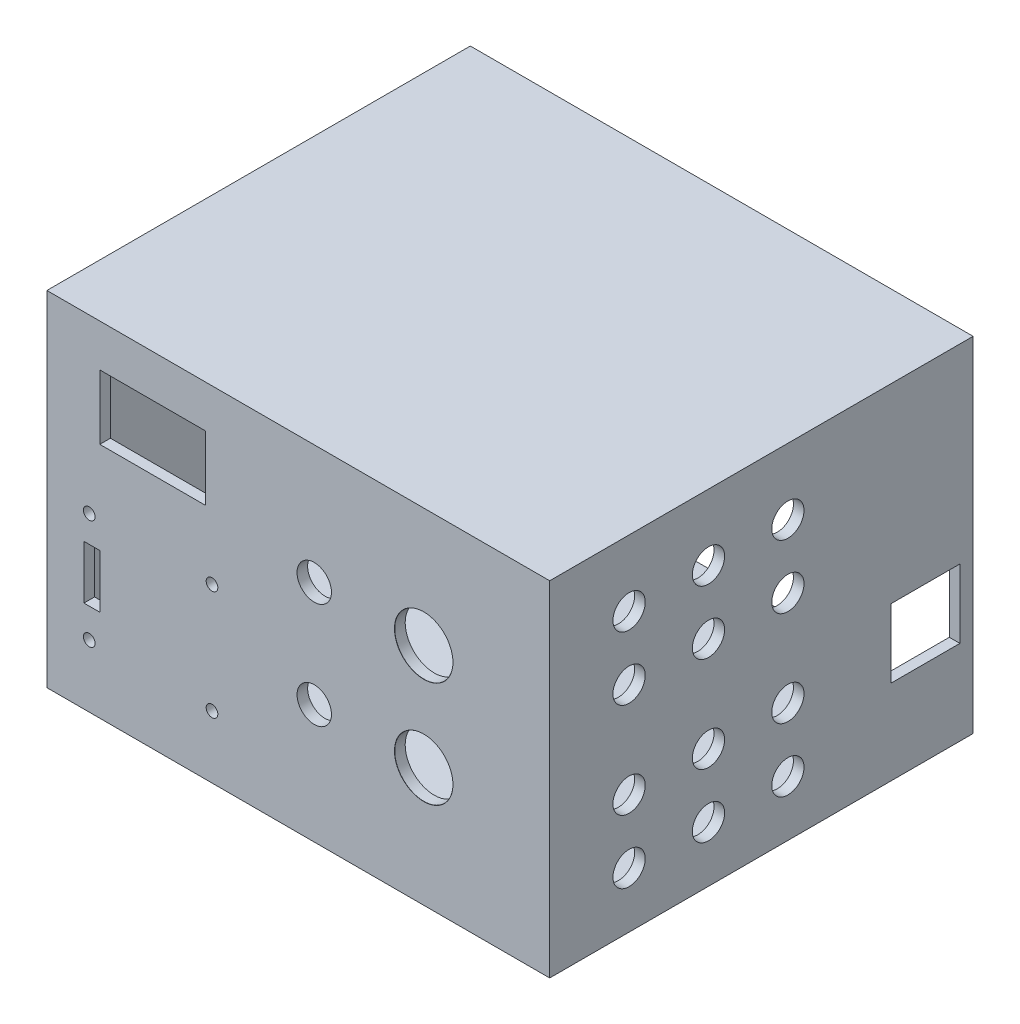
SolidWorks part; units mm, degrees
ref_plane "Plan de face" through (0, 0, 0) normal (0, 0, 1) x (1, 0, 0)
ref_plane "Plan de dessus" through (0, 0, 0) normal (0, 1, 0) x (1, 0, 0)
ref_plane "Plan de droite" through (0, 0, 0) normal (1, 0, 0) x (0, 0, -1)
sketch "Esquisse1" plane through (0, 0, 0) normal (0, 0, 1) x (1, 0, 0)
  line L0 (0, 0) -> (-47.5, 0) construction
  line L1 (-47.5, 32.5) -> (47.5, 32.5)
  line L2 (-47.5, 32.5) -> (-47.5, -32.5)
  line L3 (-47.5, -32.5) -> (47.5, -32.5)
  line L4 (47.5, 32.5) -> (47.5, -32.5)
  line L5 (-47.5, 0) -> (47.5, 0) construction
  line L6 (0, 32.5) -> (0, -32.5) construction
  dimension "D1" = 95
  dimension "D2" = 65
extrude "Boss.-Extru.1" add sketch "Esquisse1" along normal blind 83
sketch "Esquisse4" plane through (0, 0, 0) normal (0, 1, 0) x (1, 0, 0)
  line L0 (-47.5, -83) -> (-47.5, 0) construction
  line L1 (-45.5, -2) -> (45.5, -2)
  line L2 (-45.5, -2) -> (-45.5, -81)
  line L3 (-45.5, -81) -> (45.5, -81)
  line L4 (45.5, -2) -> (45.5, -81)
  line L5 (47.5, 0) -> (-47.5, 0) construction
  line L6 (47.5, -83) -> (47.5, 0) construction
  line L7 (47.5, -83) -> (-47.5, -83) construction
  dimension "D1" = 2
  dimension "D2" = 2
  dimension "D3" = 2
  dimension "D4" = 2
extrude "Enlèv. mat.-Extru.3" cut sketch "Esquisse4" against normal blind 30.5 and the other way blind 30.5
sketch "Esquisse2" plane through (0, 0, 83) normal (0, 0, 1) x (1, 0, 0)
  line L0 (0, 0) -> (-47.5, 0) construction
  line L1 (-47.5, 32.5) -> (-47.5, -32.5) construction
  line L2 (-16.3044, 32.5) -> (-16.3044, -32.5) construction
  line L3 (-37.5, 24.5) -> (-17.5, 24.5)
  line L4 (-37.5, 24.5) -> (-37.5, 12.32)
  line L5 (-37.5, 12.32) -> (-17.5, 12.32)
  line L6 (-17.5, 24.5) -> (-17.5, 12.32)
  line L7 (47.5, 32.5) -> (-47.5, 32.5) construction
  line L8 (-47.5, -32.5) -> (47.5, -32.5) construction
  line L9 (-39.5, -20.7) -> (-16.3044, -20.7) construction
  line L11 (0, 0) -> (47.5, 0) construction
  line L12 (47.5, -32.5) -> (47.5, 32.5) construction
  line L18 (-40.5, -15.15) -> (-37.5, -15.15)
  line L19 (-40.5, -15.15) -> (-40.5, -5.05)
  line L20 (-40.5, -5.05) -> (-37.5, -5.05)
  line L21 (-37.5, -15.15) -> (-37.5, -5.05)
  circle A0 centre (-39.5, 0) radius 1.1
  circle A1 centre (-39.5, -20.7) radius 1.1
  circle A2 centre (-16.3044, 0) radius 1.1
  circle A3 centre (-16.3044, -20.7) radius 1.1
  circle A4 centre (3.0156, 10) radius 3.25
  circle A5 centre (3.0156, -10) radius 3.25
  point P21 (-27.5, 12.32)
  dimension "D1" = 2.2
  dimension "D2" = 6.5
  dimension "D3" = 19.32
  dimension "D17" = 10
  dimension "D4" = 12.18
  dimension "D5" = 20
  dimension "D6" = 20.7
  dimension "D7" = 23.1956
  dimension "D8" = 8
  dimension "D9" = 23.1956
  dimension "D10" = 10
  dimension "D12" = 10.1
  dimension "D13" = 3
  dimension "D14" = 7
  dimension "D15" = 8
  dimension "D16" = 5.05
extrude "Enlèv. mat.-Extru.1" cut sketch "Esquisse2" against normal blind 10
sketch "Esquisse5" plane through (47.5, 0, 0) normal (1, 0, 0) x (0, 0, -1)
  line L0 (0, 0) -> (-83, 0) construction
  line L1 (-83, -32.5) -> (-83, 32.5) construction
  line L2 (-68, 32.5) -> (-68, -32.5) construction
  line L3 (-83, 32.5) -> (0, 32.5) construction
  line L4 (-83, -32.5) -> (0, -32.5) construction
  line L5 (-53, -32.5) -> (-53, 32.5) construction
  line L6 (-38, 32.5) -> (-38, -32.5) construction
  circle A0 centre (-68, -22) radius 3.05
  circle A1 centre (-68, -10) radius 3.05
  circle A2 centre (-53, -22) radius 3.05
  circle A3 centre (-53, -10) radius 3.05
  circle A4 centre (-38, -22) radius 3.05
  circle A5 centre (-38, -10) radius 3.05
  circle A6 centre (-68, 8) radius 3.05
  circle A7 centre (-68, 20) radius 3.05
  circle A8 centre (-53, 20) radius 3.05
  circle A9 centre (-53, 8) radius 3.05
  circle A10 centre (-38, 20) radius 3.05
  circle A11 centre (-38, 8) radius 3.05
  dimension "D1" = 6.1
  dimension "D2" = 10
  dimension "D3" = 15
  dimension "D4" = 12
  dimension "D5" = 15
  dimension "D6" = 15
  dimension "D7" = 8
  dimension "D8" = 12
  dimension "D9" = 8
  dimension "D10" = 12
  dimension "D11" = 10
  dimension "D12" = 12
  dimension "D13" = 12
  dimension "D14" = 10
  dimension "D15" = 8
  dimension "D16" = 12
extrude "Enlèv. mat.-Extru.4" cut sketch "Esquisse5" against normal blind 10
sketch "Esquisse6" plane through (47.5, 0, 0) normal (1, 0, 0) x (0, 0, -1)
  line L1 (-83, 32.5) -> (0, 32.5) construction
  line L2 (-18.5, -3.5) -> (-5.5, -3.5)
  line L3 (-18.5, -3.5) -> (-18.5, -16.5)
  line L4 (-18.5, -16.5) -> (-5.5, -16.5)
  line L5 (-5.5, -3.5) -> (-5.5, -16.5)
  line L6 (0, -32.5) -> (0, 32.5) construction
  dimension "D1" = 13
  dimension "D4" = 36
  dimension "D2" = 13
  dimension "D3" = 5.5
extrude "Enlèv. mat.-Extru.6" cut sketch "Esquisse6" against normal blind 10
hole_wizard "Dégagement M101" positions "Esquisse3D2" profile "Esquisse8" hole size "M10" standard "ISO"
sketch3d "Esquisse3D2"
  line L4 (23.6956, 32.5, 83) -> (23.6956, -32.5, 83) construction
  line L5 (47.5, 32.5, 83) -> (-47.5, 32.5, 83) construction
  line L6 (-47.5, -32.5, 83) -> (47.5, -32.5, 83) construction
  line L12 (3.0156, 10, 81) -> (3.0156, 10, 83) construction
  line L13 (3.0156, 10, 83) -> (23.6956, 10, 83) construction
  point P2 (23.6956, 10, 83)
sketch "Esquisse8" plane through (23.6956, 10, 83) normal (1, 0, 0) x (0, -1, 0)
  line L0 (0, 0) -> (0, 21.4747)
  line L1 (0, 21.4747) -> (5.5, 18.17)
  line L2 (5.5, 18.17) -> (5.5, 0.025)
  line L3 (5.5, 0.025) -> (5.525, 0)
  line L5 (5.525, 0) -> (0, 0)
  line L6 (-5.5, 0.025) -> (-5.525, 0) construction
  line L10 (0, 21.4747) -> (-5.5, 18.17) construction
  line L11 (0, -6.35) -> (0, 107.95) construction
  dimension "Diamètre du perçage" = 11
  dimension "Profondeur du perçage" = 18.17
  dimension "Diamètre du fraisage entrant" = 11.05
  dimension "Angle du fraisage entrant" = 90
  dimension "Angle de pointe" = 118
pattern_linear "Répétition linéaire1" count 2 spacing 20 along (0, -1, 0) of "Dégagement M101"
sketch "Esquisse9" plane through (47.5, 0, 0) normal (1, 0, 0) x (0, 0, -1)
  line L0 (-83, -32.5) -> (0, -32.5) construction
  line L1 (0, 32.5) -> (-3, 32.5)
  line L2 (0, 32.5) -> (0, -32.5)
  line L3 (0, -32.5) -> (-3, -32.5)
  line L4 (-3, 32.5) -> (-3, -32.5)
  dimension "D1" = 3
extrude "Enlèv. mat.-Extru.7" cut sketch "Esquisse9" against normal up to next
sketch "Esquisse10" plane through (0, 0, 3) normal (0, 0, -1) x (-1, 0, 0)
  line L0 (-45.5, 16.5) -> (-31.5, 30.5)
  line L1 (-45.5, 30.5) -> (-45.5, -30.5) construction
  line L2 (-45.5, 30.5) -> (45.5, 30.5) construction
  line L3 (45.5, 30.5) -> (-45.5, 30.5) construction
  line L4 (-45.5, 16.5) -> (-45.5, 30.5)
  line L5 (-45.5, 30.5) -> (-31.5, 30.5)
  line L6 (45.5, 16.5) -> (31.5, 30.5)
  line L7 (45.5, -30.5) -> (45.5, 30.5) construction
  line L8 (31.5, 30.5) -> (45.5, 30.5)
  line L9 (45.5, 30.5) -> (45.5, 16.5)
  line L10 (45.5, -16.5) -> (31.5, -30.5)
  line L11 (-45.5, -30.5) -> (45.5, -30.5) construction
  line L12 (31.5, -30.5) -> (45.5, -30.5)
  line L13 (45.5, -30.5) -> (45.5, -16.5)
  line L14 (-45.5, -16.5) -> (-31.5, -30.5)
  line L15 (-31.5, -30.5) -> (-45.5, -30.5)
  line L16 (-45.5, -30.5) -> (-45.5, -16.5)
  dimension "D1" = 14
  dimension "D2" = 14
  dimension "D3" = 14
  dimension "D4" = 14
  dimension "D5" = 14
  dimension "D6" = 14
  dimension "D7" = 14
  dimension "D8" = 14
extrude "Boss.-Extru.2" add sketch "Esquisse10" against normal blind 16
sketch "Esquisse11" plane through (0, 0, 3) normal (0, 0, -1) x (-1, 0, 0)
  line L0 (-47.5, 32.5) -> (-47.5, -32.5) construction
  line L1 (47.5, 32.5) -> (-47.5, 32.5) construction
  line L2 (0, 35.75) -> (0, -35.75) construction
  line L3 (45.65, 0) -> (-45.65, 0) construction
  circle A0 centre (-41.5, 26.5) radius 2
  circle A1 centre (41.5, 26.5) radius 2
  circle A2 centre (-41.5, -26.5) radius 2
  circle A3 centre (41.5, -26.5) radius 2
  dimension "D1" = 4
  dimension "D2" = 6
  dimension "D3" = 6
extrude "Enlèv. mat.-Extru.8" cut sketch "Esquisse11" against normal blind 4
chamfer "Chanfrein5" distance 10 angle 45 1 edges at (38.5, 23.5, 19)
chamfer "Chanfrein6" distance 10 angle 45 1 edges at (-38.5, -23.5, 19)
chamfer "Chanfrein7" distance 10 angle 45 1 edges at (38.5, -23.5, 19)
chamfer "Chanfrein8" distance 10 angle 45 1 edges at (-38.5, 23.5, 19)
